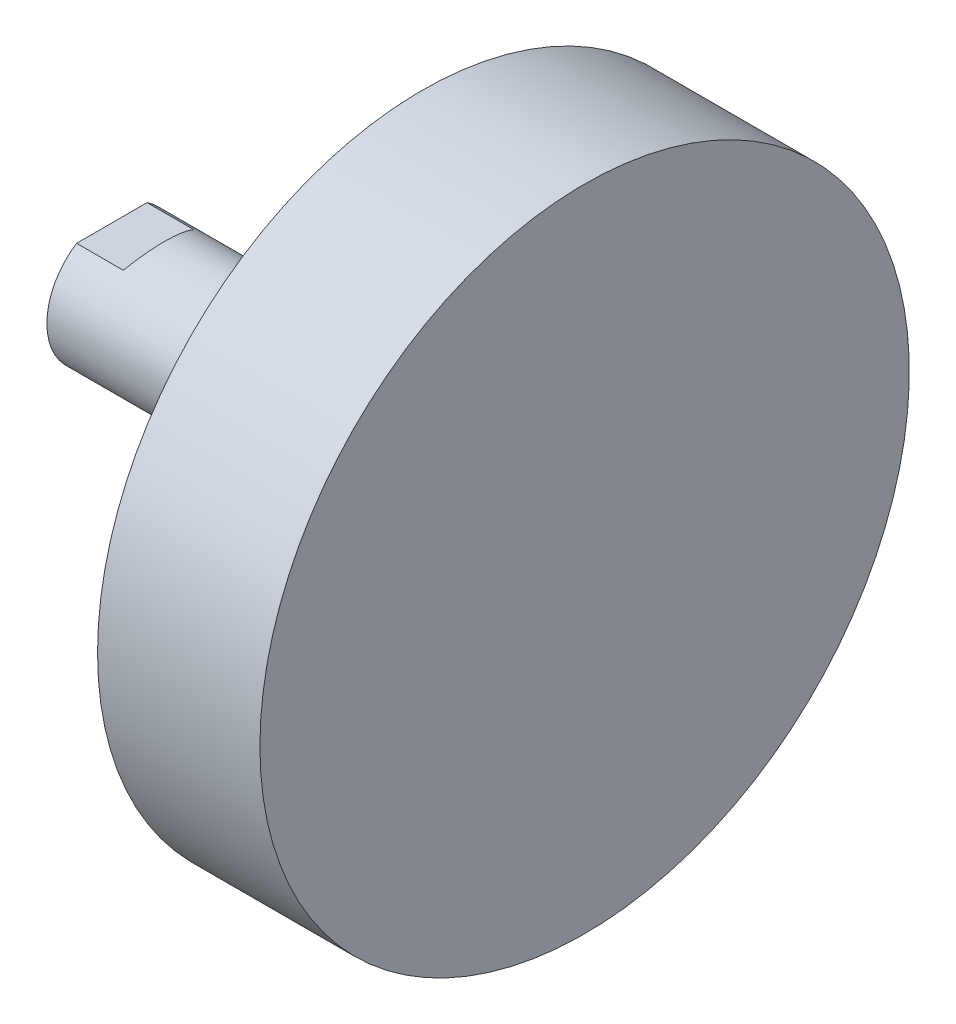
SolidWorks part; units mm, degrees
ref_plane "Front Plane" through (0, 0, 0) normal (0, 0, 1) x (1, 0, 0)
ref_plane "Top Plane" through (0, 0, 0) normal (0, 1, 0) x (1, 0, 0)
ref_plane "Right Plane" through (0, 0, 0) normal (1, 0, 0) x (0, 0, -1)
ref_plane "Plane1" through (0, 0, 0) normal (0, 0, 1) x (1, 0, 0)
sketch "Sketch1" plane through (0, 0, 0) normal (0, 0, 1) x (1, 0, 0)
  line L0 (-11, 0) -> (-11, 12.5)
  line L1 (-11, 12.5) -> (80, 12.5)
  line L2 (80, 12.5) -> (80, 0)
  line L3 (80, 0) -> (-11, 0)
  line L4 (80, 0) -> (-11, 0) construction
revolve "Revolve1" add sketch "Sketch1" angle 360 about L4 reverse direction yes
ref_plane "Plane2" through (0, 0, 0) normal (0, 0, 1) x (1, 0, 0)
sketch "Sketch2" plane through (0, 0, 0) normal (0, 0, 1) x (1, 0, 0)
  line L0 (48.75, 0) -> (48.75, 62.5)
  line L1 (48.75, 62.5) -> (80, 62.5)
  line L2 (80, 62.5) -> (80, 0)
  line L3 (80, 0) -> (48.75, 0)
  line L4 (80, 0) -> (48.75, 0) construction
revolve "Revolve2" add sketch "Sketch2" angle 360 about L4 reverse direction yes
ref_plane "Plane3" through (0, 0, 0) normal (0, 0, 1) x (1, 0, 0)
sketch "Sketch3" plane through (0, 0, 0) normal (0, 0, 1) x (1, 0, 0)
  line L0 (-67, -28) -> (8.1036, -28)
  line L1 (8.1036, -28) -> (-2, -10.5)
  line L2 (-2, -10.5) -> (-11, -10.5)
  line L3 (-11, -10.5) -> (-11, -15.5)
  line L4 (-11, -15.5) -> (-56, -15.5)
  line L5 (-56, -15.5) -> (-56, 15.5)
  line L6 (-56, 15.5) -> (-11, 15.5)
  line L7 (-11, 15.5) -> (-11, 10.5)
  line L8 (-11, 10.5) -> (-2, 10.5)
  line L9 (-2, 10.5) -> (8.1036, 28)
  line L10 (8.1036, 28) -> (-67, 28)
  line L11 (-67, 28) -> (-67, -28)
extrude "Cut-Extrude1" cut sketch "Sketch3" against normal blind 25 and the other way blind 25
ref_plane "Plane4" through (0, 0, 0) normal (0, 0, 1) x (1, 0, 0)
sketch "Sketch4" plane through (0, 0, 0) normal (0, 0, 1) x (1, 0, 0)
  line L0 (-11, 0) -> (-11, 9.5)
  line L1 (-11, 9.5) -> (-10, 8.5)
  line L2 (-10, 8.5) -> (-4, 8.5)
  line L3 (-4, 8.5) -> (-4, 8)
  line L4 (-4, 8) -> (-2.9175, 6.9175)
  line L5 (-2.9175, 6.9175) -> (20.5, 6.9175)
  line L6 (20.5, 6.9175) -> (24.4938, 0)
  line L7 (24.4938, 0) -> (-11, 0)
  line L8 (24.4938, 0) -> (-11, 0) construction
revolve "Cut-Revolve1" cut sketch "Sketch4" angle 360 about L8 reverse direction yes
cosmetic thread "Cosmetic Thread1" parameters "D1"=18, "D2"=16
